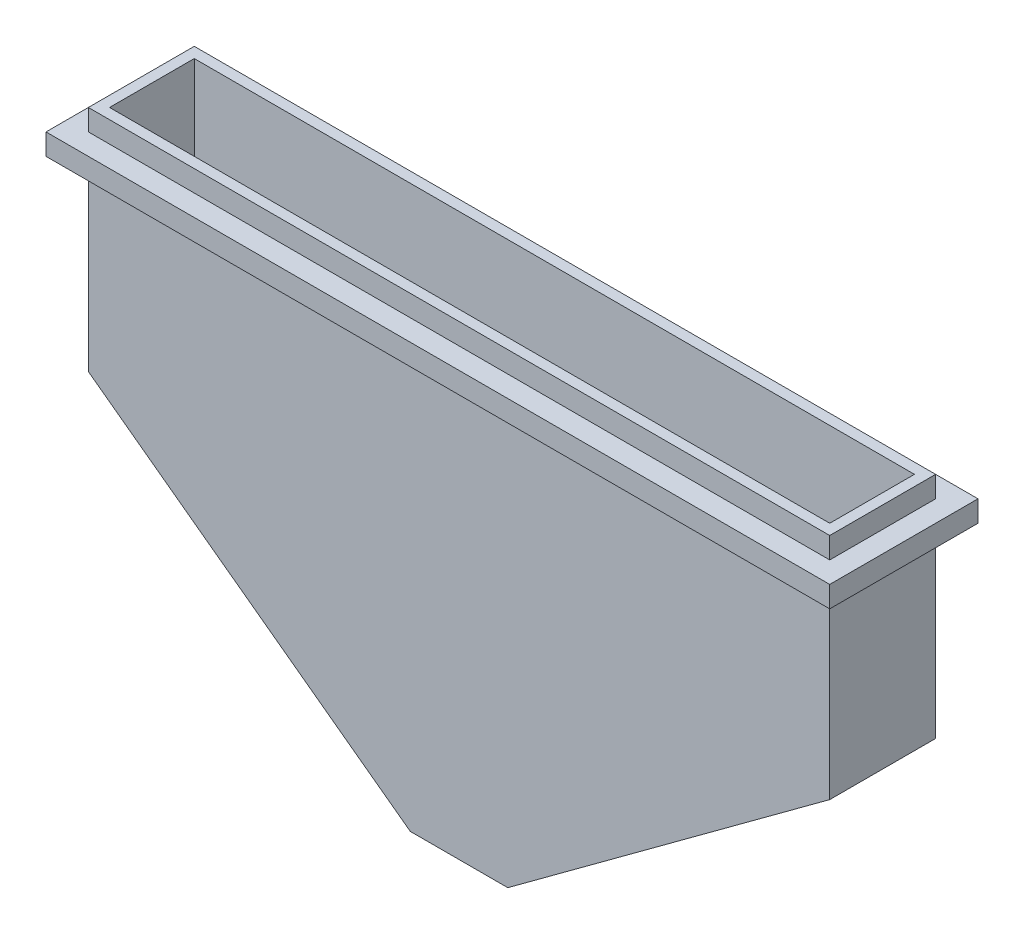
SolidWorks part; units mm, degrees
material "灰铸铁"
ref_plane "前视基准面" through (0, 0, 0) normal (0, 0, 1) x (1, 0, 0)
ref_plane "上视基准面" through (0, 0, 0) normal (0, 1, 0) x (1, 0, 0)
ref_plane "右视基准面" through (0, 0, 0) normal (1, 0, 0) x (0, 0, -1)
sketch "草图1" plane through (0, 0, 0) normal (0, 1, 0) x (1, 0, 0)
  line L1 (-185, 35) -> (185, 35)
  line L2 (-185, 35) -> (-185, -35)
  line L3 (-185, -35) -> (185, -35)
  line L4 (185, 35) -> (185, -35)
  line L5 (-185, 35) -> (185, -35) construction
  line L6 (-185, -35) -> (185, 35) construction
  point P0 (0, 0)
  dimension "D1" = 370
  dimension "D2" = 70
extrude "凸台-拉伸1" add sketch "草图1" along normal blind 10
sketch "草图2" plane through (0, 10, 0) normal (0, 1, 0) x (1, 0, 0)
  line L1 (-175, 25) -> (175, 25)
  line L2 (-175, 25) -> (-175, -25)
  line L3 (-175, -25) -> (175, -25)
  line L4 (175, 25) -> (175, -25)
  line L5 (-175, 25) -> (175, -25) construction
  line L6 (-175, -25) -> (175, 25) construction
  point P0 (0, 0)
  dimension "D1" = 350
  dimension "D2" = 50
extrude "凸台-拉伸2" add sketch "草图2" along normal blind 10
sketch "草图3" plane through (0, 0, 0) normal (0, -1, 0) x (1, 0, 0)
  line L4 (-175, -25) -> (175, -25)
  line L5 (175, -25) -> (175, 25)
  line L6 (175, 25) -> (-175, 25)
  line L7 (-175, 25) -> (-175, -25)
  line L8 (-175, -25) -> (175, -25)
  line L9 (175, -25) -> (175, 25)
  line L10 (175, 25) -> (-175, 25)
  line L11 (-175, 25) -> (-175, -25)
  dimension "D1" = 0
extrude "凸台-拉伸3" add sketch "草图3" along normal blind 200
sketch "草图4" plane through (0, -200, 0) normal (0, -1, 0) x (1, 0, 0)
  circle A0 centre (0, 0) radius 12.5
  dimension "D1" = 25
chamfer "倒角1" distance 112 distance2 152 2 edges at (175, -200, 0) (-175, -200, 0) first distance on face at (175, -100, 0) first distance on face at (-175, -100, 0)
shell "抽壳1" thickness 5 removed face at (0, 20, 0)
extrude "切除-拉伸1" cut sketch "草图4" against normal blind 30 contours A0
